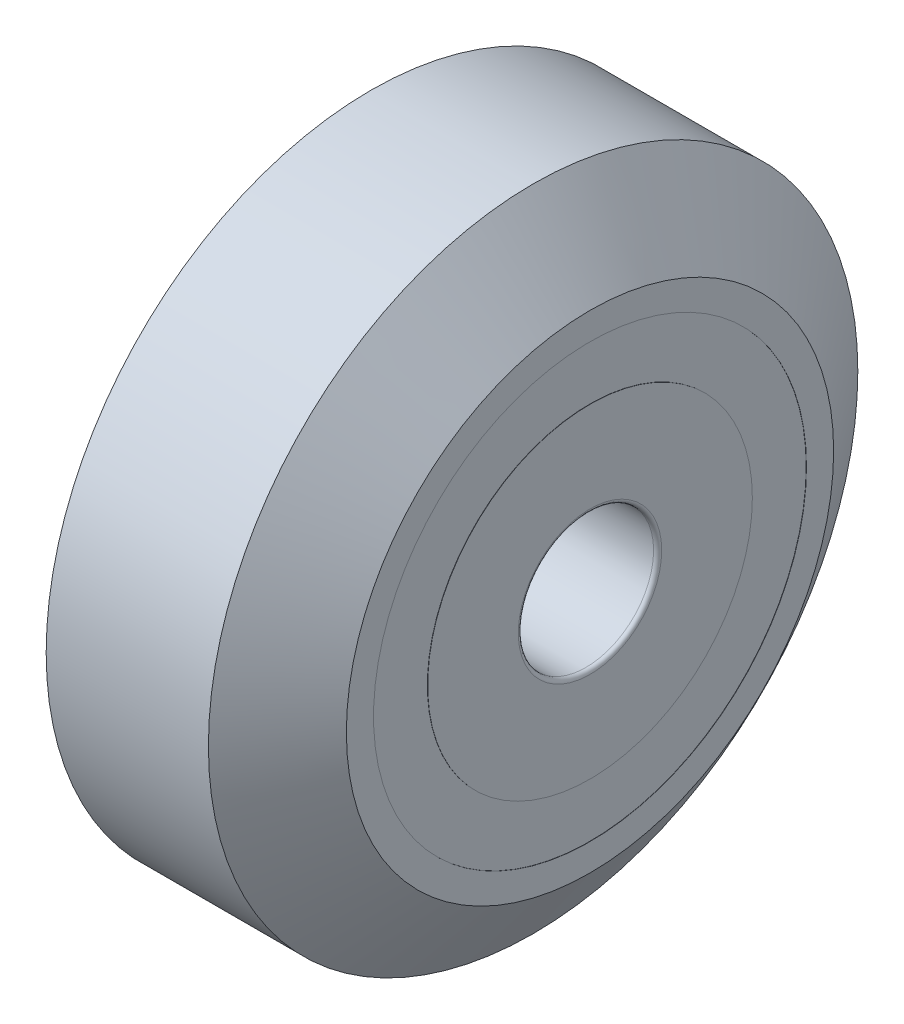
SolidWorks part; units mm, degrees
material "1.4000 (X6Cr13)"
ref_plane "Plan de face" through (0, 0, 0) normal (0, 0, 1) x (1, 0, 0)
ref_plane "Plan de dessus" through (0, 0, 0) normal (0, 1, 0) x (1, 0, 0)
ref_plane "Plan de droite" through (0, 0, 0) normal (1, 0, 0) x (0, 0, -1)
ref_plane "Plan1" through (5.1, 0, 0) normal (1, 0, 0) x (0, 0, -1)
sketch "Esquisse9" plane through (5.1, 0, 0) normal (1, 0, 0) x (0, 0, -1)
  circle A0 centre (0, 0) radius 12
extrude "Boss.-Extru.2" add sketch "Esquisse9" along normal blind 5.1 and the other way blind 5.1
sketch "Esquisse10" plane through (10.2, 0, 0) normal (1, 0, 0) x (0, 0, -1)
  circle A0 centre (0, 0) radius 2.5
extrude "Enlèv. mat.-Extru.3" cut sketch "Esquisse10" against normal through all
sketch "Esquisse11" plane through (0, 0, 0) normal (0, 0, 1) x (1, 0, 0)
  line L0 (5.1, -12) -> (8.0977, -12) construction
  line L1 (0, -12) -> (10.2, -12) construction
  line L2 (5.1, -12) -> (2.1026, -12) construction
  line L3 (0, -12) -> (0, -9.0039) construction
  line L4 (0, 12) -> (0, -12) construction
  line L5 (0, -9.0039) -> (2.1026, -12) construction
  line L6 (0, -9.0039) -> (10.2, -9.0039) construction
  line L7 (10.2, -12) -> (10.2, 12) construction
  line L8 (10.2, -9.0039) -> (8.0977, -12) construction
  line L9 (10.2, 0) -> (0, 0) construction
  line L10 (0, -9.0039) -> (2.1026, -12)
  line L11 (2.1026, -12) -> (8.0977, -12)
  line L12 (8.0977, -12) -> (10.2, -9.0039)
  line L13 (10.2, -9.0039) -> (10.2, -12)
  line L14 (10.2, -12) -> (7.9487, -12.3108)
  line L15 (7.9487, -12.3108) -> (2.0204, -12.3108)
  line L16 (2.0204, -12.3108) -> (0, -12)
  line L17 (0, -12) -> (0, -9.0039)
  line L18 (10.2, 12) -> (7.9487, 12.3108)
  line L19 (10.2, 9.0039) -> (10.2, 12)
  line L20 (8.0977, 12) -> (10.2, 9.0039)
  line L21 (2.1026, 12) -> (8.0977, 12)
  line L22 (0, 9.0039) -> (2.1026, 12)
  line L23 (0, 12) -> (0, 9.0039)
  line L24 (2.0204, 12.3108) -> (0, 12)
  line L25 (7.9487, 12.3108) -> (2.0204, 12.3108)
revolve "Enlèvement de matière-Révolution1" cut sketch "Esquisse11" angle 360 about L9
fillet "Congé1" radius 0.15 1 edges at (10.2, 0, -2.5)
sketch "Esquisse13" plane through (10.2, 0, 0) normal (1, 0, 0) x (0, 0, -1)
  circle A0 centre (0, 0) radius 8
  circle A1 centre (0, 0) radius 6
extrude "Enlèv. mat.-Extru.4" cut sketch "Esquisse13" against normal blind 0.01
sketch "Esquisse14" plane through (0, 0, 0) normal (-1, 0, 0) x (0, 0, 1)
  circle A0 centre (0, 0) radius 8
  circle A1 centre (0, 0) radius 6
extrude "Enlèv. mat.-Extru.5" cut sketch "Esquisse14" against normal blind 0.01
